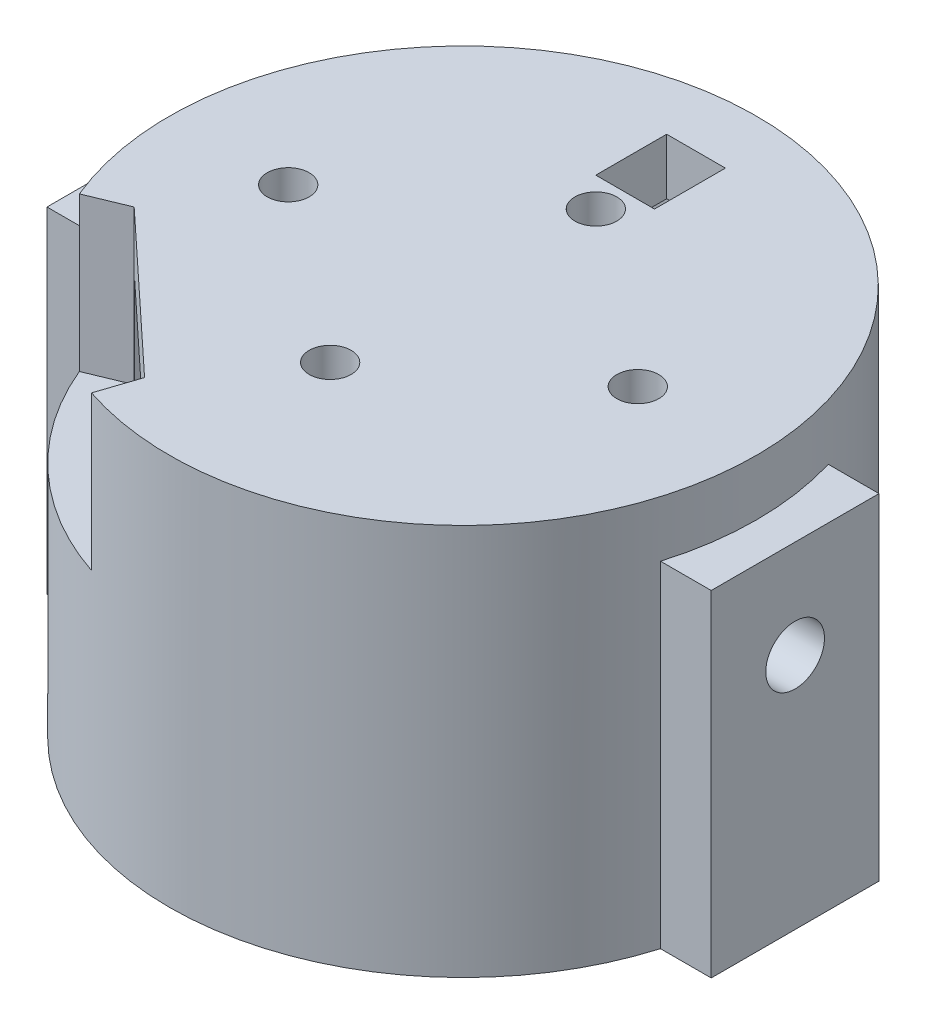
SolidWorks part; units mm, degrees
ref_plane "Front Plane" through (0, 0, 0) normal (0, 0, 1) x (1, 0, 0)
ref_plane "Top Plane" through (0, 0, 0) normal (0, 1, 0) x (1, 0, 0)
ref_plane "Right Plane" through (0, 0, 0) normal (1, 0, 0) x (0, 0, -1)
sketch "Sketch1" plane through (0, 0, 0) normal (0, 1, 0) x (1, 0, 0)
  circle A0 centre (0, 0) radius 17.75
  circle A1 centre (0, 0) radius 21
  dimension "D1" = 35.5
  dimension "D2" = 42
extrude "Boss-Extrude2" add sketch "Sketch1" along normal mid plane 24
sketch "Sketch5" plane through (0, 0, 0) normal (0, 1, 0) x (1, 0, 0)
  line L5 (17.75, 6) -> (23.75, 6)
  line L6 (17.75, 6) -> (17.75, -6)
  line L7 (17.75, -6) -> (23.75, -6)
  line L8 (23.75, 6) -> (23.75, -6)
  line L9 (17.75, 6) -> (23.75, -6) construction
  line L10 (17.75, -6) -> (23.75, 6) construction
  circle A0 centre (0, 0) radius 17.75 construction
  point P0 (20.75, 0)
  point P7 (0, 0)
  dimension "D1" = 6
  dimension "D2" = 12
extrude "Boss-Extrude7" add sketch "Sketch5" along normal mid plane 24 separate body
sketch "Sketch6" plane through (0, 0, 0) normal (0, 1, 0) x (1, 0, 0)
  line L5 (-23.75, 6) -> (-17.75, 6)
  line L6 (-23.75, 6) -> (-23.75, -6)
  line L7 (-23.75, -6) -> (-17.75, -6)
  line L8 (-17.75, 6) -> (-17.75, -6)
  line L9 (-23.75, 6) -> (-17.75, -6) construction
  line L10 (-23.75, -6) -> (-17.75, 6) construction
  circle A0 centre (0, 0) radius 17.75 construction
  point P0 (-20.75, 0)
  point P7 (0, 0)
  dimension "D1" = 12
  dimension "D2" = 6
extrude "Boss-Extrude8" add sketch "Sketch6" along normal mid plane 24
sketch "Sketch7" plane through (0, 0, 6) normal (0, 0, 1) x (1, 0, 0)
  circle A0 centre (0, 0) radius 2.1
  dimension "D1" = 4.2
sketch "Sketch8" plane through (0, 12, 0) normal (0, 1, 0) x (1, 0, 0)
  circle A0 centre (0, 0) radius 21
  dimension "D1" = 42
extrude "Boss-Extrude9" add sketch "Sketch8" along normal blind 4
sketch "Sketch9" plane through (0, 16, 0) normal (0, 1, 0) x (1, 0, 0)
  circle A0 centre (0, 0) radius 9.5 construction
  circle A2 centre (0, 9.5) radius 1.5
  circle A3 centre (0, -9.5) radius 1.5
  circle A4 centre (0, 0) radius 12.5 construction
  circle A5 centre (-12.5, 0) radius 1.5
  circle A6 centre (12.5, 0) radius 1.5
  dimension "D1" = 19
  dimension "D2" = 3
  dimension "D3" = 3
  dimension "D4" = 25
  dimension "D5" = 3
  dimension "D6" = 3
extrude "Cut-Extrude2" cut sketch "Sketch9" against normal up to next
sketch "Sketch12" plane through (0, 0, 0) normal (0, 1, 0) x (1, 0, 0)
  line L0 (-19.4037, -8.031) -> (-16.6317, -6.8837)
  line L1 (-6.6458, -19.9207) -> (-5.6964, -17.0749)
  line L2 (-5.6964, -17.0749) -> (-16.6317, -6.8837)
  arc A0 (-19.4037, -8.031) -> (-6.6458, -19.9207) centre (0, 0) ccw
  circle A1 centre (0, 0) radius 21 construction
  point P7 (-6.6458, -19.9207)
  dimension "D2" = 3
  dimension "D1" = 3
extrude "Cut-Extrude6" cut sketch "Sketch12" along normal through all from offset 5
sketch "Sketch13" plane through (-23.75, 0, 0) normal (-1, 0, 0) x (0, 0, 1)
  circle A0 centre (0, 5) radius 2.1
  point P3 (0, 0)
  point P5 (0, 0)
  dimension "D1" = 4.2
  dimension "D2" = 5
extrude "Cut-Extrude7" cut sketch "Sketch13" against normal through all
sketch "Sketch14" plane through (0, 16, 0) normal (0, 1, 0) x (1, 0, 0)
  line L1 (-2.1, 16.6645) -> (2.1, 16.6645)
  line L2 (-2.1, 16.6645) -> (-2.1, 11.5934)
  line L3 (-2.1, 11.5934) -> (2.1, 11.5934)
  line L4 (2.1, 16.6645) -> (2.1, 11.5934)
  line L5 (-2.1, 16.6645) -> (2.1, 11.5934) construction
  line L6 (-2.1, 11.5934) -> (2.1, 16.6645) construction
  point P0 (0, 14.129)
  point P5 (0, 0)
  dimension "D1" = 4.2
extrude "Cut-Extrude9" cut sketch "Sketch14" against normal blind 10
